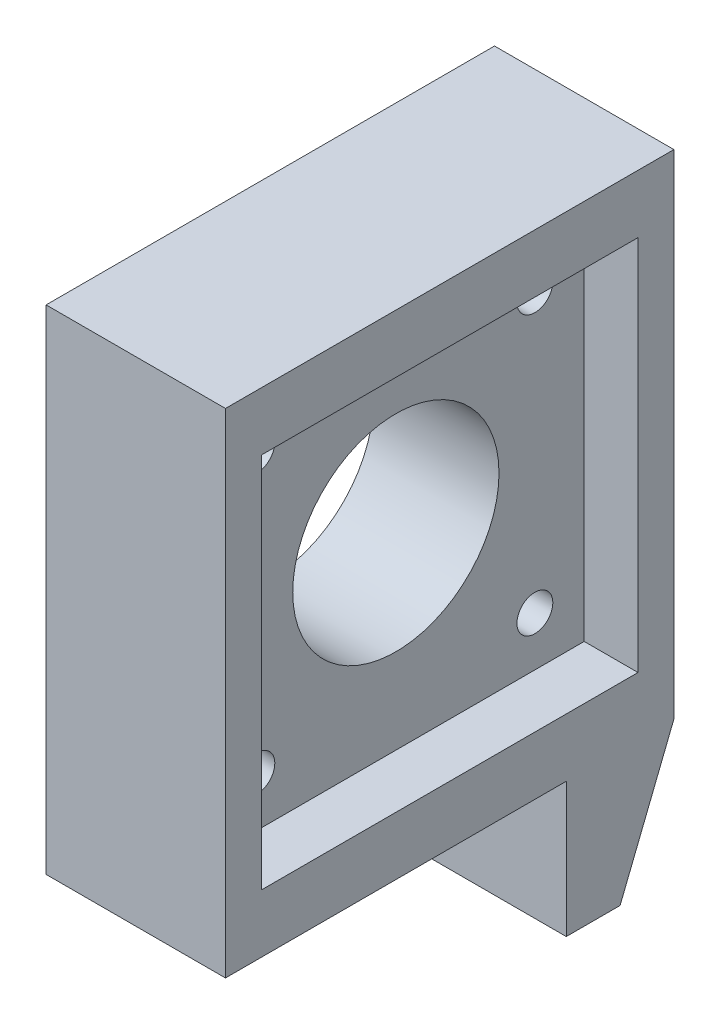
SolidWorks part; units mm, degrees
ref_plane "Front Plane" through (0, 0, 0) normal (0, 0, 1) x (1, 0, 0)
ref_plane "Top Plane" through (0, 0, 0) normal (0, 1, 0) x (1, 0, 0)
ref_plane "Right Plane" through (0, 0, 0) normal (1, 0, 0) x (0, 0, -1)
sketch "Sketch1" plane through (0, 0, 0) normal (0, 1, 0) x (1, 0, 0)
  line L1 (0, 0) -> (-20, 0)
  line L2 (0, 0) -> (0, -50)
  line L3 (0, -50) -> (-20, -50)
  line L4 (-20, 0) -> (-20, -50)
  dimension "D1" = 20
  dimension "D2" = 50
extrude "Boss-Extrude1" add sketch "Sketch1" along normal blind 70
sketch "Sketch2" plane through (0, 0, 0) normal (1, 0, 0) x (0, 0, -1)
  line L0 (-50, 70) -> (0, 70) construction
  line L1 (0, 70) -> (0, 0) construction
  line L2 (0, 42.5) -> (-50, 42.5) construction
  line L3 (-25, 70) -> (-25, 0) construction
  line L4 (-25, 70) -> (-25, 0) construction
  line L7 (-50, 70) -> (-50, 0) construction
  circle A0 centre (-9.5, 58) radius 2
  circle A4 centre (-25, 42.5) radius 11.5
  circle A5 centre (-9.5, 27) radius 2
  circle A8 centre (-40.5, 27) radius 2
  circle A9 centre (-40.5, 58) radius 2
  dimension "D1" = 4
  dimension "D2" = 12
  dimension "D3" = 15.5
  dimension "D6" = 23
  dimension "D7" = 0
  dimension "D8" = 0
  dimension "D4" = 15.5
  dimension "D5" = 0
extrude "Cut-Extrude2" cut sketch "Sketch2" against normal blind 60
sketch "Sketch4" plane through (0, 0, 0) normal (1, 0, 0) x (0, 0, -1)
  line L1 (-50, 0) -> (-12, 0)
  line L2 (-50, 0) -> (-50, 15)
  line L3 (-50, 15) -> (-12, 15)
  line L4 (-12, 0) -> (-12, 15)
  circle A0 centre (-25, 42.5) radius 11.5 construction
  dimension "D1" = 15
  dimension "D2" = 13
extrude "Cut-Extrude3" cut sketch "Sketch4" against normal blind 60
sketch "Sketch8" plane through (0, 0, 0) normal (0, 0, -1) x (-1, 0, 0)
  line L0 (0, 0) -> (20, 0) construction
  line L1 (20, 70) -> (20, 0) construction
  circle A0 centre (15, 6) radius 2
  dimension "D1" = 4
  dimension "D2" = 6
  dimension "D3" = 5
extrude "Cut-Extrude5" cut sketch "Sketch8" against normal blind 15
sketch "Sketch9" plane through (0, 0, 0) normal (1, 0, 0) x (0, 0, -1)
  line L0 (0, 42.5) -> (-50, 42.5) construction
  line L1 (-4, 63.5) -> (-46, 63.5)
  line L2 (-4, 63.5) -> (-4, 21.5)
  line L3 (-4, 21.5) -> (-46, 21.5)
  line L4 (-46, 63.5) -> (-46, 21.5)
  line L5 (0, 70) -> (0, 0) construction
  line L6 (-50, 70) -> (-50, 15) construction
  line L7 (-25, 70) -> (-25, 15) construction
  line L8 (-50, 70) -> (0, 70) construction
  line L9 (-12, 15) -> (-50, 15) construction
  circle A0 centre (-25, 42.5) radius 11.5 construction
  dimension "D1" = 0
  dimension "D2" = 42
  dimension "D3" = 21
  dimension "D4" = 42
  dimension "D5" = 21
  dimension "D6" = 0
extrude "Cut-Extrude6" cut sketch "Sketch9" against normal blind 6
sketch "Sketch10" plane through (0, 0, 0) normal (0, 0, -1) x (-1, 0, 0)
  line L0 (0, 70) -> (0, 0) construction
  circle A0 centre (5, 6) radius 2
  circle A1 centre (15, 6) radius 2 construction
  dimension "D1" = 4
  dimension "D2" = 5
  dimension "D3" = 0
extrude "Cut-Extrude7" cut sketch "Sketch10" against normal blind 7
sketch "Sketch11" plane through (0, 0, 0) normal (1, 0, 0) x (0, 0, -1)
  line L7 (-6, 0) -> (0, 0)
  line L8 (-12, 0) -> (0, 0) construction
  line L9 (0, 0) -> (0, 15)
  line L10 (0, 70) -> (0, 0) construction
  line L11 (0, 15) -> (-6, 0)
  line L12 (-12, 15) -> (-50, 15) construction
  dimension "D1" = 0
  dimension "D2" = 6
extrude "Cut-Extrude8" cut sketch "Sketch11" against normal blind 30
